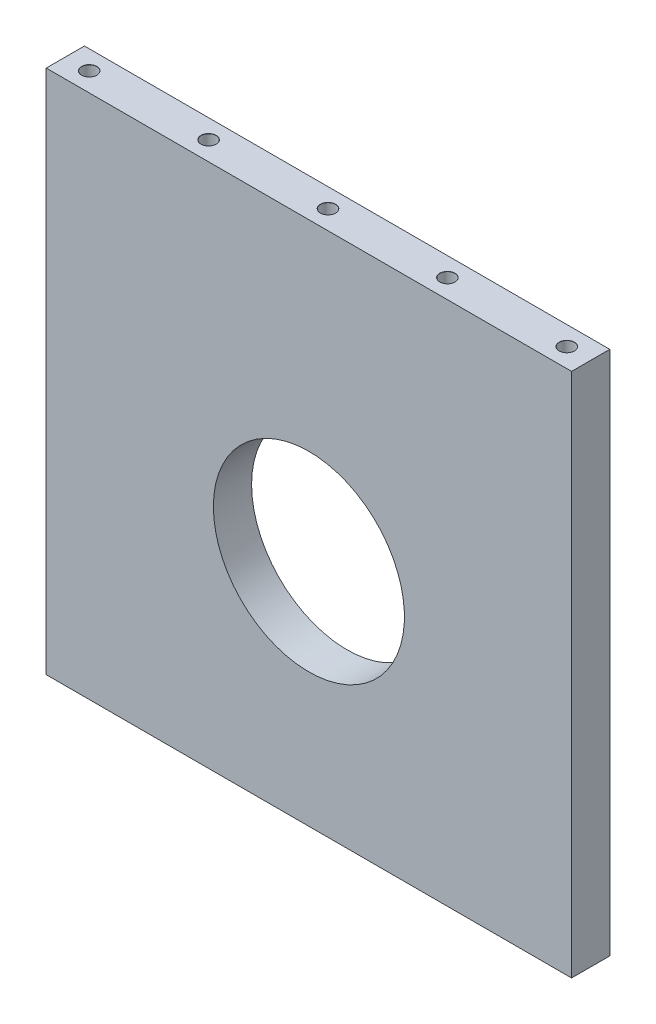
SolidWorks part; units mm, degrees
material "6061-T6 (SS)"
ref_plane "Front Plane" through (0, 0, 0) normal (0, 0, 1) x (1, 0, 0)
ref_plane "Top Plane" through (0, 0, 0) normal (0, 1, 0) x (1, 0, 0)
ref_plane "Right Plane" through (0, 0, 0) normal (1, 0, 0) x (0, 0, -1)
sketch "Sketch1" plane through (0, 0, 0) normal (0, 0, 1) x (1, 0, 0)
  line L1 (0, 0) -> (110, 0)
  line L2 (0, 0) -> (0, 110)
  line L3 (0, 110) -> (110, 110)
  line L4 (110, 0) -> (110, 110)
  dimension "D1" = 110
  dimension "D2" = 110
extrude "Boss-Extrude1" add sketch "Sketch1" along normal blind 8
sketch "Sketch2" plane through (0, 110, 0) normal (0, 1, 0) x (1, 0, 0)
  line L0 (0, -4) -> (110, -4) construction
  line L1 (0, -8) -> (0, 0) construction
  line L2 (110, -8) -> (110, 0) construction
  point P9 (55, -4)
  point P18 (80, -4)
  point P19 (105, -4)
  point P20 (55, -4)
  point P21 (80, -4)
  point P22 (30, -4)
  point P23 (55, -4)
  point P24 (30, -4)
  point P25 (5, -4)
  dimension "D1" = 3
  dimension "D2" = 3
hole_wizard "Tap Drill for M3 Helicoil1" positions "Sketch2" profile "Sketch4" hole size "M3x0.5" standard "DIN"
sketch "Sketch4" plane through (5, 110, 4) normal (1, 0, 0) x (0, 0, 1)
  line L0 (0, 0) -> (0, 6.9464)
  line L1 (0, 6.9464) -> (1.575, 6)
  line L2 (1.575, 6) -> (1.575, 0.025)
  line L3 (1.575, 0.025) -> (1.6, 0)
  line L5 (1.6, 0) -> (0, 0)
  line L6 (-1.575, 0.025) -> (-1.6, 0) construction
  line L10 (0, 6.9464) -> (-1.575, 6) construction
  line L11 (0, -6.35) -> (0, 107.95) construction
  dimension "Hole Dia." = 3.15
  dimension "Hole Depth" = 6
  dimension "Near C'Sink Dia." = 3.2
  dimension "Near C'Sink Angle" = 90
  dimension "Drill Angle" = 118
sketch "Sketch5" plane through (0, 0, 0) normal (0, 0, -1) x (-1, 0, 0)
  circle A0 centre (-55, 48) radius 40 construction
  point P8 (-55, 48)
hole_wizard "Ø40.0 (40) Diameter Hole1" positions "Sketch5" profile "Sketch7" hole size "Ø40.0" standard "DIN" end condition through all
sketch "Sketch7" plane through (55, 48, 0) normal (1, 0, 0) x (0, 1, 0)
  line L0 (0, 0) -> (0, 8)
  line L1 (0, 8) -> (20, 8)
  line L2 (20, 8) -> (20, 0)
  line L5 (20, 0) -> (0, 0)
  line L11 (0, -6.35) -> (0, 107.95) construction
  dimension "Thru Hole Dia." = 40
  dimension "Thru Hole Depth" = 8
